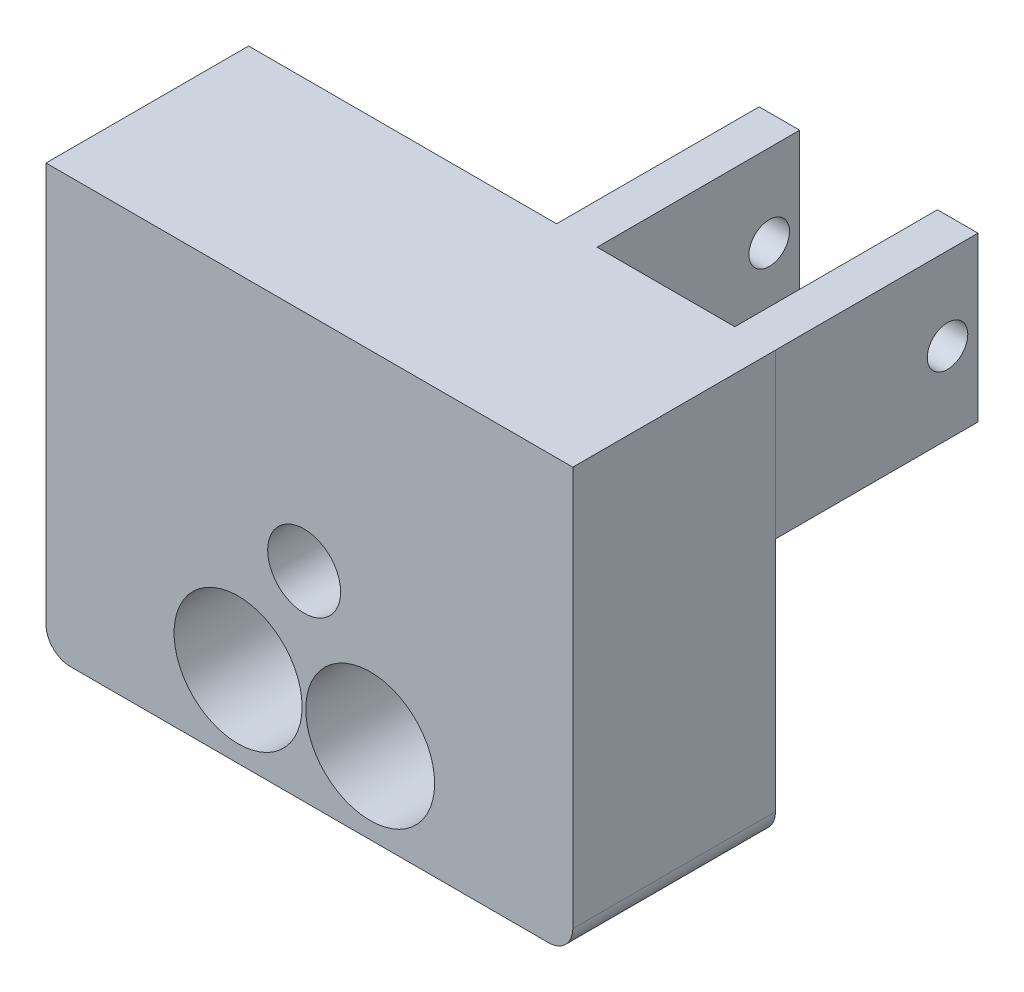
SolidWorks part; units mm, degrees
ref_plane "Plan de face" through (0, 0, 0) normal (0, 0, 1) x (1, 0, 0)
ref_plane "Plan de dessus" through (0, 0, 0) normal (0, 1, 0) x (1, 0, 0)
ref_plane "Plan de droite" through (0, 0, 0) normal (1, 0, 0) x (0, 0, -1)
sketch "Esquisse1" plane through (0, 0, 0) normal (0, 0, 1) x (1, 0, 0)
  line L1 (0, 0) -> (105, 0)
  line L2 (0, 0) -> (0, 80)
  line L3 (0, 80) -> (105, 80)
  line L4 (105, 0) -> (105, 80)
  dimension "D1" = 80
  dimension "D2" = 105
extrude "Boss.-Extru.1" add sketch "Esquisse1" along normal blind 25
sketch "Esquisse2" plane through (0, 0, 0) normal (0, 0, 1) x (1, 0, 0)
  line L0 (0, 0) -> (105, 0) construction
  line L1 (105, 0) -> (105, 80) construction
  line L2 (0, 0) -> (105, 0) construction
  circle A0 centre (63.7, 10) radius 7.9
  circle A1 centre (80, 10) radius 7.95
  circle A2 centre (71.85, 24.6335) radius 4.5
  dimension "D1" = 9
  dimension "D2" = 15.9
  dimension "D3" = 15.8
  dimension "D12" = 10
  dimension "D4" = 16.3
  dimension "D5" = 16.75
  dimension "D6" = 16.75
  dimension "D7" = 10
  dimension "D8" = 25
extrude "Enlèv. mat.-Extru.1" cut sketch "Esquisse2" along normal through all
sketch "Esquisse3" plane through (0, 0, 0) normal (0, 1, 0) x (1, 0, 0)
  line L1 (105, -25) -> (105, 0) construction
  line L2 (0, 0) -> (105, 0) construction
  circle A0 centre (49, -12.5) radius 4
  circle A1 centre (93, -12.5) radius 4
  dimension "D1" = 8
  dimension "D2" = 8
  dimension "D4" = 12
  dimension "D6" = 12.5
  dimension "D3" = 44
  dimension "D5" = 12.5
extrude "Enlèv. mat.-Extru.3" cut sketch "Esquisse3" along normal blind 10
sketch "Esquisse6" plane through (0, 0, 0) normal (0, 0, 1) x (1, 0, 0)
  line L0 (0, 0) -> (105, 0) construction
  line L1 (40, 0) -> (0, 0)
  line L2 (40, 0) -> (40, 80)
  line L3 (40, 80) -> (0, 80)
  line L4 (0, 0) -> (0, 80)
  dimension "D1" = 40
extrude "Enlèv. mat.-Extru.6" cut sketch "Esquisse6" along normal through all
sketch "Esquisse7" plane through (0, 0, 0) normal (0, 0, 1) x (1, 0, 0)
  line L0 (40, 0) -> (40, 80) construction
  line L1 (105, 80) -> (40, 80)
  line L2 (105, 80) -> (105, 77.3119)
  line L3 (105, 77.3119) -> (40, 77.3119)
  line L4 (40, 80) -> (40, 77.3119)
extrude "Enlèv. mat.-Extru.7" cut sketch "Esquisse7" along normal through all
fillet "Congé1" radius 3 4 edges at (105, 77.3119, 12.5) (40, 77.3119, 12.5) (40, 0, 12.5) (105, 0, 12.5)
sketch "Esquisse9" plane through (0, 0, 0) normal (0, 0, 1) x (1, 0, 0)
  line L0 (43, 77.3119) -> (102, 77.3119) construction
  line L1 (104.9917, 32.1324) -> (99.9917, 32.1324)
  line L2 (104.9917, 32.1324) -> (104.9917, 52.3119)
  line L3 (104.9917, 52.3119) -> (99.9917, 52.3119)
  line L4 (99.9917, 32.1324) -> (99.9917, 52.3119)
  line L5 (82.9917, 52.3119) -> (77.9917, 52.3119)
  line L6 (82.9917, 52.3119) -> (82.9917, 32.1319)
  line L7 (82.9917, 32.1319) -> (77.9917, 32.1319)
  line L8 (77.9917, 52.3119) -> (77.9917, 32.1319)
  point P8 (102.4917, 52.3119)
  point P11 (80.4917, 52.3119)
  dimension "D1" = 17
  dimension "D2" = 2.5
  dimension "D3" = 5
  dimension "D4" = 20.1794
  dimension "D5" = 25
  dimension "D6" = 25
  dimension "D7" = 20.18
extrude "Boss.-Extru.2" add sketch "Esquisse9" against normal blind 25
sketch "Esquisse10" plane through (104.9917, 0, 0) normal (1, 0, 0) x (0, 0, -1)
  line L0 (0, 32.1324) -> (0, 52.3119) construction
  line L1 (25, 32.1324) -> (0, 32.1324) construction
  circle A0 centre (21.24, 42.1324) radius 2.5
  point P5 (0, 42.2222)
  dimension "D1" = 5
  dimension "D2" = 21.24
  dimension "D3" = 10
extrude "Enlèv. mat.-Extru.8" cut sketch "Esquisse10" against normal through all
sketch "Esquisse11" plane through (0, 0, 0) normal (0, 0, -1) x (-1, 0, 0)
  line L1 (-73.3817, 32.158) -> (-79.1322, 27.0693)
  line L2 (-79.1322, 27.0693) -> (-77.6005, 19.5448)
  line L3 (-77.6005, 19.5448) -> (-70.3183, 17.1091)
  line L4 (-70.3183, 17.1091) -> (-64.5678, 22.1978)
  line L5 (-64.5678, 22.1978) -> (-66.0995, 29.7222)
  line L6 (-66.0995, 29.7222) -> (-73.3817, 32.158)
  circle A0 centre (-71.85, 24.6335) radius 6.65 construction
  dimension "D1" = 13.3
extrude "Enlèv. mat.-Extru.9" cut sketch "Esquisse11" against normal blind 7.5
sketch "Esquisse12" plane through (0, 0, 0) normal (0, 0, -1) x (-1, 0, 0)
  line L0 (-105.676, 77.3306) -> (-105.676, 52.3119)
  line L1 (-104.9917, 52.3119) -> (-39.9853, 52.3119)
  line L2 (-105.676, 52.3119) -> (-104.9917, 52.3119)
  line L3 (-104.9917, 77.3306) -> (-39.9853, 77.3306)
  line L4 (-39.9853, 52.3119) -> (-39.9853, 77.3306)
  line L5 (-104.9917, 77.3306) -> (-105.676, 77.3306)
extrude "Enlèv. mat.-Extru.11" cut sketch "Esquisse12" against normal through all
